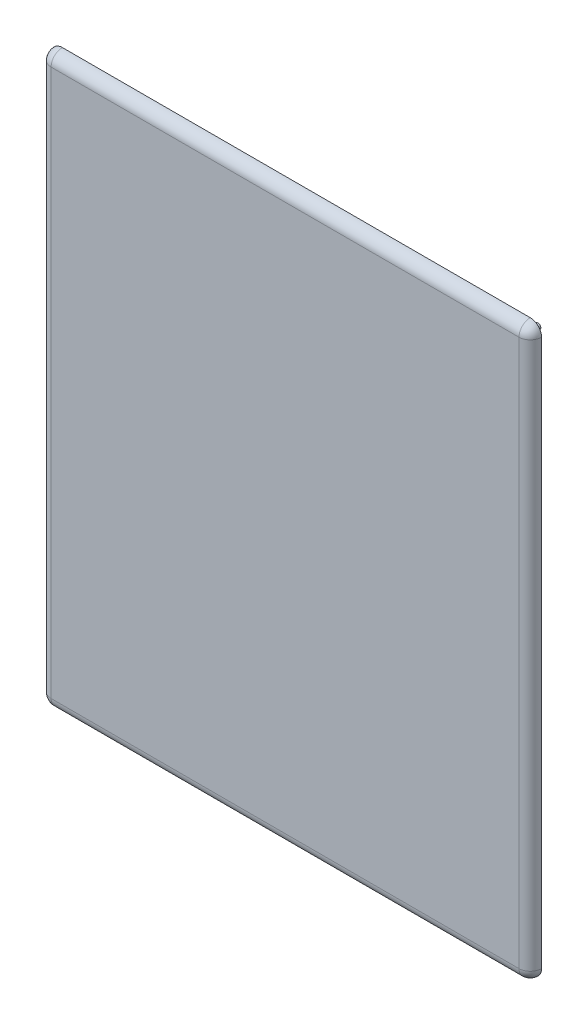
SolidWorks part; units mm, degrees
ref_plane "Front Plane" through (0, 0, 0) normal (0, 0, 1) x (1, 0, 0)
ref_plane "Top Plane" through (0, 0, 0) normal (0, 1, 0) x (1, 0, 0)
ref_plane "Right Plane" through (0, 0, 0) normal (1, 0, 0) x (0, 0, -1)
sketch "Sketch1" plane through (0, 0, 0) normal (0, 0, 1) x (1, 0, 0)
  line L1 (0, 0) -> (220.98, 0)
  line L2 (0, 0) -> (0, 256.54)
  line L3 (0, 256.54) -> (220.98, 256.54)
  line L4 (220.98, 0) -> (220.98, 256.54)
  dimension "D1" = 256.54
  dimension "D2" = 220.98
extrude "Boss-Extrude1" add sketch "Sketch1" along normal blind 5.08
fillet "Fillet1" radius 5.08 4 edges at (110.49, 0, 5.08) (220.98, 128.27, 5.08) (0, 128.27, 5.08) (110.49, 256.54, 5.08)
fillet "Fillet2" radius 5.08 4 edges at (1.4879, 1.4879, 3.5921) (219.4921, 1.4879, 3.5921) (219.4921, 255.0521, 3.5921) (1.4879, 255.0521, 3.5921)
sketch "Sketch2" plane through (0, 0, 0) normal (0, 0, -1) x (-1, 0, 0)
  line L0 (-110.49, 7.9375) -> (-110.49, 0) construction
  line L1 (-5.08, 0) -> (-215.9, 0) construction
  line L2 (-213.0425, 128.27) -> (-220.98, 128.27) construction
  line L3 (-220.98, 5.08) -> (-220.98, 251.46) construction
  line L4 (-7.9375, 128.27) -> (0, 128.27) construction
  line L5 (0, 251.46) -> (0, 5.08) construction
  line L10 (-110.49, 248.6025) -> (-110.49, 256.54) construction
  line L11 (-213.0425, 248.6025) -> (-7.9375, 248.6025) construction
  line L12 (-213.0425, 248.6025) -> (-213.0425, 7.9375) construction
  line L13 (-213.0425, 7.9375) -> (-7.9375, 7.9375) construction
  line L14 (-7.9375, 248.6025) -> (-7.9375, 7.9375) construction
  line L15 (-215.9, 256.54) -> (-5.08, 256.54) construction
  circle A0 centre (-213.0425, 248.6025) radius 1.27
  circle A1 centre (-7.9375, 248.6025) radius 1.27
  circle A2 centre (-213.0425, 7.9375) radius 1.27
  circle A3 centre (-7.9375, 7.9375) radius 1.27
  dimension "D3" = 2.54
  dimension "D1" = 7.9375
  dimension "D2" = 7.9375
extrude "Boss-Extrude2" add sketch "Sketch2" along normal blind 6.35
